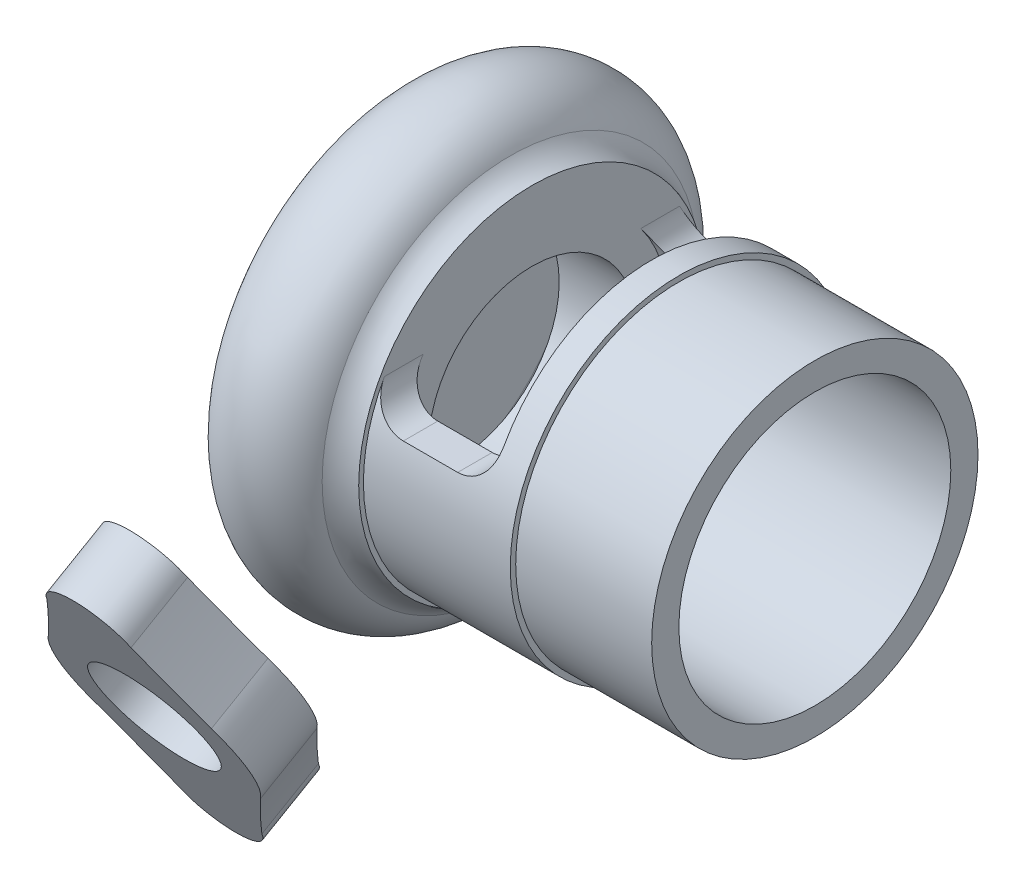
SolidWorks part; units mm, degrees
ref_plane "Front Plane" through (0, 0, 0) normal (0, 0, 1) x (1, 0, 0)
ref_plane "Top Plane" through (0, 0, 0) normal (0, 1, 0) x (1, 0, 0)
ref_plane "Right Plane" through (0, 0, 0) normal (1, 0, 0) x (0, 0, -1)
sketch "Sketch1" plane through (0, 0, 0) normal (0, 0, 1) x (1, 0, 0)
  line L0 (-49, 0) -> (49, 0) construction
  line L1 (49, 0) -> (49, 25) construction
  line L2 (49, 25) -> (19, 25)
  line L3 (19, 25) -> (19, 31)
  line L4 (19, 31) -> (24, 31)
  line L5 (24, 31) -> (24, 30)
  line L6 (24, 30) -> (49, 30)
  line L7 (49, 30) -> (49, 25)
revolve "Revolve1" add sketch "Sketch1" angle 360 about L0
sketch "Sketch3" plane through (19, 0, 0) normal (-1, 0, 0) x (0, 0, 1)
  circle A1 centre (0, 0) radius 31
  circle A2 centre (0, 0) radius 31
  circle A3 centre (0, 0) radius 25
  circle A4 centre (0, 0) radius 31
  circle M2 centre (0, 0) radius 25
  circle M3 centre (0, 0) radius 31
  dimension "D1" = 0
extrude "Boss-Extrude1" add sketch "Sketch3" along normal blind 22 contours M3 M2 region at (19, 0, -30.1232)
sketch "Sketch4" plane through (0, 0, 0) normal (0, 0, 1) x (1, 0, 0)
  line L0 (-3, 31) -> (19, 31)
  line L1 (24, 31) -> (-3, 31) construction
  line L2 (-3, 31) -> (-3, 15)
  line L3 (-3, 31) -> (-3, -31) construction
  line L4 (3, 9) -> (13, 9)
  line L5 (19, 15) -> (19, 31)
  arc A0 (13, 9) -> (19, 15) centre (13, 15) ccw
  arc A1 (3, 9) -> (-3, 15) centre (3, 15) cw
  point P13 (-3, 9)
  dimension "D1" = 6
extrude "Cut-Extrude1" cut sketch "Sketch4" against normal through all both and the other way through all
sketch "Sketch10" plane through (0, 0, 0) normal (0, 0, 1) x (1, 0, 0)
  line L0 (49, 30) -> (49, 10.2608) construction
  line L1 (49, -30) -> (49, 30) construction
  line L2 (49, 30) -> (49, -30) construction
  line L3 (49, 0) -> (-60.8461, 0) construction
  line L4 (-3, 19) -> (-3, 31.8677)
  line L5 (-28, 0) -> (-25, 0)
  line L7 (-17, 38.0042) -> (-17, 38)
  line L8 (-25, 30) -> (-25, 0)
  line L9 (-28, 30) -> (-28, 0)
  line L10 (-17, 22) -> (-17, 19)
  line L12 (-17, 19) -> (-3, 19)
  arc A0 (-17, 22) -> (-25, 30) centre (-17, 30) ccw
  arc A1 (-7.0011, 34.585) -> (-28, 30) centre (-17, 30) ccw
  arc A2 (-7.0011, 34.585) -> (-3, 31.8677) centre (-1.3458, 38.6078) ccw
  dimension "D1" = 8
revolve "Revolve2" add sketch "Sketch10" angle 360 about L3
sketch "Sketch11" plane through (0, 0, 0) normal (1, 0, 0) x (0, 0, -1)
  line L0 (0, 0) -> (-16.9842, 0) construction
  line L1 (0, 0) -> (-55.4256, -32)
  dimension "D1" = 64
  dimension "D2" = 210
ref_plane "Plane5" through (0, -32, 55.4256) normal (0, -0.5, 0.866) x (1, 0, 0)
sketch "Sketch12" plane through (0, -32, 55.4256) normal (0, -0.5, 0.866) x (1, 0, 0)
  line L2 (-17, 0) -> (-17, -17.5) construction
  line L4 (-17, 0) -> (-17, 44.3251) construction
  arc A0 (-9.2709, 24.0642) -> (-24.7291, 24.0642) centre (-17, 22) ccw
  arc A1 (-2.0099, 9.0304) -> (-2.0099, -9.0304) centre (-17, 0) cw
  circle A2 centre (-17, 0) radius 11
  arc A3 (-31.9901, 9.0304) -> (-24.7291, 24.0642) centre (-285.7816, 140.8758) ccw
  arc A4 (-2.0099, 9.0304) -> (-9.2709, 24.0642) centre (251.7816, 140.8758) cw
  arc A5 (-31.9901, 9.0304) -> (-31.9901, -9.0304) centre (-17, 0) ccw
  arc A6 (-2.0099, -9.0304) -> (-9.2709, -24.0642) centre (251.7816, -140.8758) ccw
  arc A7 (-31.9901, -9.0304) -> (-24.7291, -24.0642) centre (-285.7816, -140.8758) cw
  arc A8 (-9.2709, -24.0642) -> (-24.7291, -24.0642) centre (-17, -22) cw
extrude "Boss-Extrude2" add sketch "Sketch12" against normal blind 12 separate body
